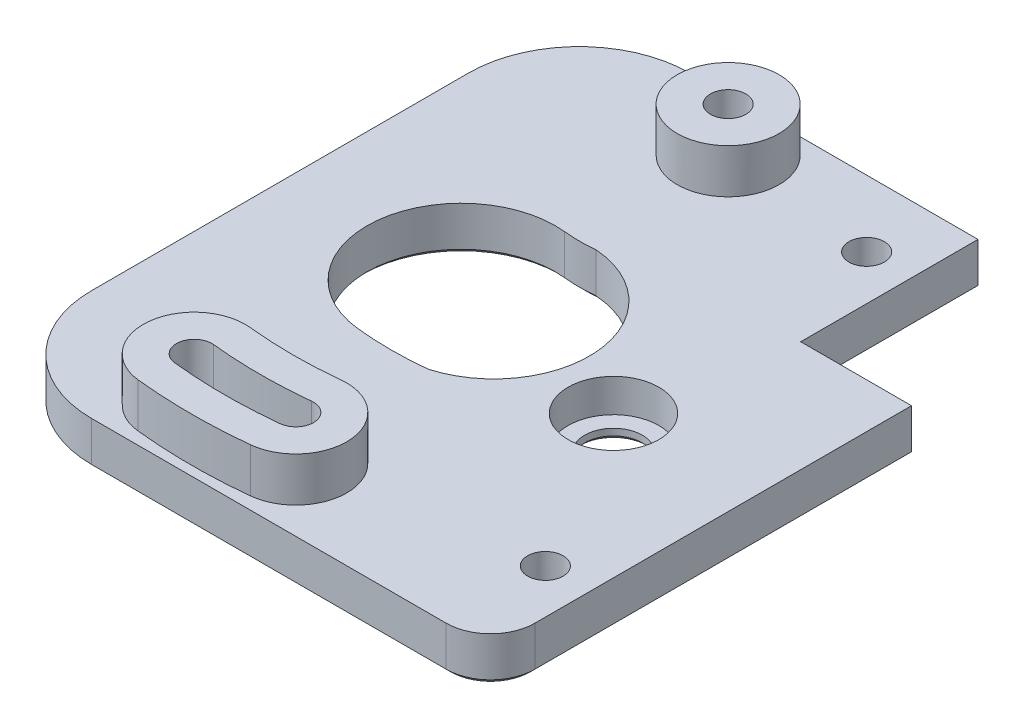
SolidWorks part; units mm, degrees
ref_plane "前视基准面" through (0, 0, 0) normal (0, 0, 1) x (1, 0, 0)
ref_plane "上视基准面" through (0, 0, 0) normal (0, 1, 0) x (1, 0, 0)
ref_plane "右视基准面" through (0, 0, 0) normal (1, 0, 0) x (0, 0, -1)
other "Configuration Table"
sketch "草图1" plane through (0, 0, 0) normal (0, 1, 0) x (1, 0, 0)
  line L1 (0, 0) -> (46, 0)
  line L2 (0, 0) -> (0, 54)
  line L3 (0, 54) -> (46, 54)
  line L4 (46, 0) -> (46, 54)
  dimension "D1" = 46
  dimension "D2" = 54
extrude "凸台-拉伸1" add sketch "草图1" along normal blind 4
sketch "草图2" plane through (0, 0, 0) normal (0, -1, 0) x (-1, 0, 0)
  line L0 (0, 54) -> (0, 0) construction
  line L1 (-46, 54) -> (0, 54) construction
  circle A0 centre (-18.15, 49.3) radius 1.6
  circle A1 centre (-18.15, 5.45) radius 1.6
  circle A2 centre (-18.15, 27.375) radius 8.5
  circle A3 centre (-33.15, 23.95) radius 4.1
  point P6 (0, 27)
  point P9 (-23, 54)
  dimension "D7" = 17
  dimension "D10" = 8.2
  dimension "D11" = 3.2
  dimension "D12" = 3.2
  dimension "D1" = 22.3
  dimension "D2" = 4.85
  dimension "D3" = 0
  dimension "D4" = 43.85
  dimension "D5" = 0
  dimension "D6" = 21.925
  dimension "D8" = 15
  dimension "D9" = 18.5
extrude "切除-拉伸1" cut sketch "草图2" against normal through all
sketch "草图4" plane through (0, 0, 0) normal (0, -1, 0) x (-1, 0, 0)
  circle A0 centre (-33.15, 23.95) radius 4.1
  circle A1 centre (-33.15, 23.95) radius 2.6
  dimension "D1" = 5.2
extrude "凸台-拉伸2" add sketch "草图4" against normal blind 1
sketch "草图5" plane through (0, 4, 0) normal (0, 1, 0) x (1, 0, 0)
  line L0 (46, 0) -> (46, 54) construction
  line L1 (46, 54) -> (36, 54)
  line L2 (46, 54) -> (46, 38)
  line L3 (46, 38) -> (36, 38)
  line L4 (36, 54) -> (36, 38)
  line L5 (46, 54) -> (0, 54) construction
  dimension "D1" = 16
  dimension "D2" = 10
extrude "切除-拉伸2" cut sketch "草图5" against normal through all
sketch "草图6" plane through (0, 0, 0) normal (0, -1, 0) x (-1, 0, 0)
  circle A0 centre (-18.15, 49.3) radius 43.85 construction
  circle A7 centre (-18.15, 49.3) radius 21.925 construction
  arc A8 (-22.5663, 7.2814) -> (-13.7337, 7.2814) centre (-18.15, 49.3) ccw
  arc A10 (-21.3303, 19.0417) -> (-14.9697, 19.0417) centre (-18.15, 49.3) ccw
  arc A11 (-19.5533, 35.9485) -> (-16.7467, 35.9485) centre (-18.15, 49.3) ccw
  arc A13 (-19.5533, 35.9485) -> (-21.3303, 19.0417) centre (-18.9549, 27.3388) ccw
  arc A14 (-14.9697, 19.0417) -> (-16.7467, 35.9485) centre (-15.8582, 27.4951) ccw
  arc A17 (-22.9008, 4.099) -> (-13.3992, 4.099) centre (-18.15, 49.3) ccw
  arc A18 (-22.5663, 7.2814) -> (-22.9008, 4.099) centre (-22.7336, 5.6902) ccw
  arc A19 (-13.3992, 4.099) -> (-13.7337, 7.2814) centre (-13.5664, 5.6902) ccw
  point P4 (-18.15, 49.3)
  point P5 (24.1, 49.3)
  point P6 (-18.15, 49.3)
  point P8 (27.3, 49.3)
  point P15 (-18.15, 49.3)
  point P18 (-18.15, 49.3)
  point P21 (-18.15, 49.3)
  point P24 (-18.15, 49.3)
  point P31 (-18.15, 49.3)
  point P34 (-18.15, 49.3)
extrude "切除-拉伸3" cut sketch "草图6" against normal blind 10
sketch "草图7" plane through (0, 4, 0) normal (0, 1, 0) x (1, 0, 0)
  circle A1 centre (18.15, 49.3) radius 4.6
  circle A2 centre (18.15, 49.3) radius 1.6
  circle A3 centre (18.15, 49.3) radius 1.6
  arc A13 (14.0473, 10.265) -> (22.2527, 10.265) centre (18.15, 49.3) ccw
  arc A14 (23.2144, 1.1154) -> (22.2527, 10.265) centre (22.7336, 5.6902) ccw
  arc A15 (13.0856, 1.1154) -> (23.2144, 1.1154) centre (18.15, 49.3) ccw
  arc A16 (14.0473, 10.265) -> (13.0856, 1.1154) centre (13.5664, 5.6902) ccw
  arc A17 (22.9008, 4.099) -> (22.5663, 7.2814) centre (22.7336, 5.6902) ccw
  arc A18 (13.7337, 7.2814) -> (13.3992, 4.099) centre (13.5664, 5.6902) ccw
  arc A19 (13.3992, 4.099) -> (22.9008, 4.099) centre (18.15, 49.3) ccw
  arc A20 (13.7337, 7.2814) -> (22.5663, 7.2814) centre (18.15, 49.3) ccw
  arc A21 (22.9008, 4.099) -> (22.5663, 7.2814) centre (22.7336, 5.6902) ccw
  arc A22 (13.7337, 7.2814) -> (13.3992, 4.099) centre (13.5664, 5.6902) ccw
  arc A23 (13.3992, 4.099) -> (22.9008, 4.099) centre (18.15, 49.3) ccw
  arc A24 (13.7337, 7.2814) -> (22.5663, 7.2814) centre (18.15, 49.3) ccw
  dimension "D1" = 0
  dimension "D2" = 3
  dimension "D3" = 0
  dimension "D4" = 3
extrude "凸台-拉伸3" add sketch "草图7" along normal blind 4
sketch "草图10" plane through (0, 4, 0) normal (0, 1, 0) x (1, 0, 0)
  line L0 (46, 0) -> (46, 38) construction
  line L1 (0, 0) -> (46, 0) construction
  circle A1 centre (42, 8.95) radius 1.6
  dimension "D1" = 4
  dimension "D2" = 8.95
  dimension "D3" = 3.2
extrude "切除-拉伸6" cut sketch "草图10" against normal through all
sketch "草图11" plane through (0, 4, 0) normal (0, 1, 0) x (1, 0, 0)
  line L1 (36, 54) -> (0, 54) construction
  circle A0 centre (31.95, 48) radius 1.6
  circle A1 centre (18.15, 49.3) radius 4.6 construction
  dimension "D1" = 3.2
  dimension "D2" = 13.8
  dimension "D3" = 6
extrude "切除-拉伸7" cut sketch "草图11" against normal through all
fillet "圆角1" radius 10 2 edges at (0, 2, -54) (0, 2, 0)
fillet "圆角2" radius 4 1 edges at (46, 2, 0)
chamfer "倒角1" distance 0.4 angle 45 21 edges at (7.4048, 0, -28.3836) (18.15, 0, -35.875) (27.5381, 0, -28.241) (18.15, 0, -18.875) (33.15, 0, -26.55) (18.15, 0, -50.9) (41, 0, -38) (36, 0, -46) (23, 0, -54) (2.9289, 0, -51.0711) (0, 0, -27) (2.9289, 0, -2.9289) (26, 0, 0) (44.8284, 0, -1.1716) (46, 0, -21) (42, 0, -7.35) (31.95, 0, -46.4) (11.9752, 0, -5.8575) (18.15, 0, -7.05) (24.3248, 0, -5.8575) (18.15, 0, -3.85)
equation "\"D6@草图2\"=\"D4@草图2\"/2"
equation "\"D1@凸台-拉伸2\"=3.60-2.6"
